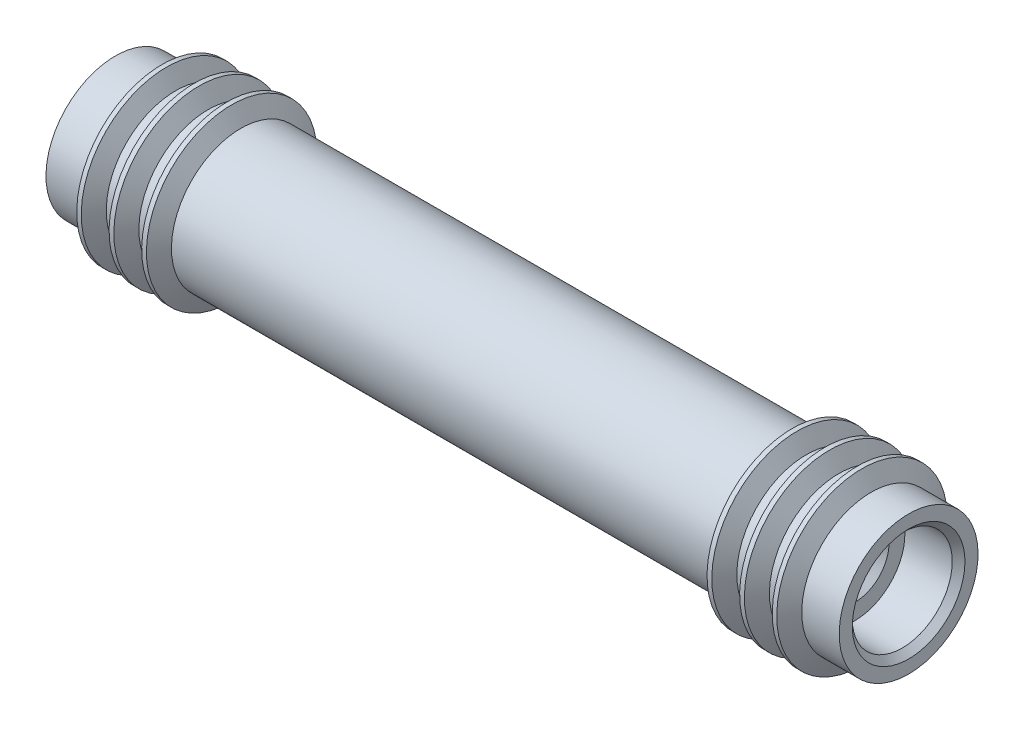
SolidWorks part; units mm, degrees
ref_plane "Front Plane" through (0, 0, 0) normal (0, 0, 1) x (1, 0, 0)
ref_plane "Top Plane" through (0, 0, 0) normal (0, 1, 0) x (1, 0, 0)
ref_plane "Right Plane" through (0, 0, 0) normal (1, 0, 0) x (0, 0, -1)
sketch "Sketch2" plane through (0, 0, 0) normal (0, 0, 1) x (1, 0, 0)
  line L0 (0, 0) -> (0, 28.4375) construction
  line L1 (-31.75, 4) -> (-27.45, 4) construction
  line L2 (-31.75, 4) -> (-31.75, -4) construction
  line L3 (-31.75, -4) -> (-27.45, -4) construction
  line L4 (-27.45, 4) -> (-27.45, -4) construction
  line L5 (-31.75, 4) -> (-27.45, -4) construction
  line L6 (-31.75, -4) -> (-27.45, 4) construction
  line L7 (27.45, 4.5) -> (36.1332, 4.5) construction
  line L8 (27.45, 4.5) -> (27.45, -4.5) construction
  line L9 (27.45, -4.5) -> (36.1332, -4.5) construction
  line L10 (36.1332, 4.5) -> (36.1332, -4.5) construction
  line L11 (27.45, 4.5) -> (36.1332, -4.5) construction
  line L12 (27.45, -4.5) -> (36.1332, 4.5) construction
  line L13 (-31.75, 0) -> (36.1332, 0) construction
  line L14 (-31.75, 5.5562) -> (-28.75, 5.5562)
  line L15 (-28.75, 5.5562) -> (-28.0168, 6.8262)
  line L16 (-28.0168, 6.8262) -> (-27.6572, 6.8262)
  line L19 (-25.4288, 6.8262) -> (-25.0478, 6.8263)
  line L20 (-25.0478, 6.8263) -> (-24.3145, 5.5562)
  line L21 (-20.3302, 3.175) -> (0, 3.175) construction
  line L22 (-31.75, 5.5562) -> (-31.75, 4)
  line L23 (-31.75, 4) -> (-27.45, 4)
  line L24 (-27.45, 4) -> (-27.45, 0)
  line L25 (-27.45, 0) -> (0, 0)
  line L26 (0, 0) -> (0, 3.175)
  line L27 (-33.2419, -5.5563) -> (-33.2419, 5.5562) construction
  line L28 (-26.543, 5.5562) -> (-26.543, 7.68) construction
  line L29 (-26.543, 5.5562) -> (26.543, 5.5562) construction
  line L30 (-31.75, 5.5562) -> (31.75, 5.5562) construction
  line L31 (0, 1.6) -> (-12.5, 1.6) construction
  line L32 (-12.5, 1.6) -> (-14.1, 0) construction
  line L33 (-12.5, 1.6) -> (-12.5, -1.6) construction
  line L34 (-12.5, 1.6) -> (12.5, 1.6) construction
  line L35 (-27.45, 1.7145) -> (-21.925, 1.7145)
  line L36 (-21.925, 1.7145) -> (-21.925, 0)
  line L37 (-27.45, 2.73) -> (-26.942, 2.222)
  line L38 (-21.925, 1.7145) -> (-34.925, 1.7145) construction
  line L39 (-21.925, 1.7145) -> (-21.925, -1.7145) construction
  line L40 (-21.925, -1.7145) -> (-34.925, -1.7145) construction
  line L41 (-34.925, 1.7145) -> (-34.925, -1.7145) construction
  line L42 (-26.942, 2.222) -> (-26.942, 0)
  line L43 (-26.924, 5.5562) -> (-26.162, 5.5562)
  line L44 (-27.6572, 6.8262) -> (-26.924, 5.5562)
  line L45 (-25.4288, 6.8262) -> (-26.162, 5.5562)
  line L46 (-24.3145, 5.5562) -> (-23.5525, 5.5562)
  line L47 (-23.5525, 5.5562) -> (-22.8193, 6.8263)
  line L48 (-22.8193, 6.8263) -> (-22.4383, 6.8263)
  line L49 (-22.4383, 6.8263) -> (-21.7051, 5.5562)
  line L50 (-24.3145, 5.5562) -> (-22.9397, 3.175) construction
  line L51 (-23.9335, 5.5562) -> (-23.9335, 7.9749) construction
  line L52 (-22.9397, 3.175) -> (-20.3302, 3.175) construction
  line L53 (-21.7051, 5.5562) -> (0, 5.5562)
  line L54 (0, 5.5562) -> (0, 3.175)
  line L55 (-21.7051, 5.5562) -> (-20.3302, 3.175) construction
  point P0 (-29.6, 0)
  point P5 (31.7916, 0)
  point P27 (-33.2419, 0)
  point P29 (-12.5, 0)
  point P33 (0, 5.5562)
  point P36 (0, 1.6)
  point P48 (-21.925, 0)
  point P51 (0, 5.5562)
  point P53 (-26.543, 5.5562)
  dimension "D1" = 4.3
  dimension "D4" = 11.1125
  dimension "D5" = 8
  dimension "D6" = 60
  dimension "D7" = 60
  dimension "D8" = 1.27
  dimension "D9" = 60
  dimension "D10" = 53.086
  dimension "D11" = 63.5
  dimension "D12" = 0.381
  dimension "D13" = 45
  dimension "D14" = 25
  dimension "D16" = 3.429
  dimension "D17" = 3.175
  dimension "D18" = 1.27
  dimension "D19" = 0.508
  dimension "D20" = 45
  dimension "D21" = 13
  dimension "D22" = 3
  dimension "D23" = 0.762
  dimension "D24" = 0.381
revolve "Revolve1" add sketch "Sketch2" angle 360 about L13 region at (-14.0222, 3.0753, 0)
chamfer "Chamfer1" distance 0.508 angle 45 1 edges at (-31.75, -4, 0)
mirror "Mirror1" about plane through (0, 0, 0) normal (1, 0, 0) of bodies 101
